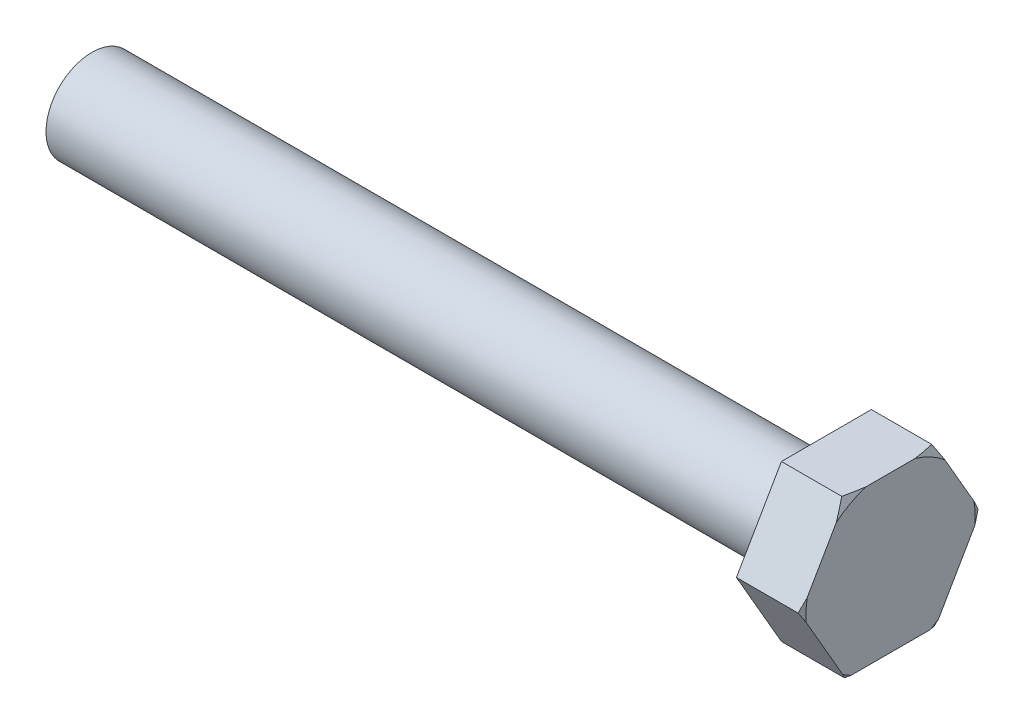
SolidWorks part; units mm, degrees
ref_plane "Front Plane" through (0, 0, 0) normal (0, 0, 1) x (1, 0, 0)
ref_plane "Top Plane" through (0, 0, 0) normal (0, 1, 0) x (1, 0, 0)
ref_plane "Right Plane" through (0, 0, 0) normal (1, 0, 0) x (0, 0, -1)
sketch "Sketch1" plane through (0, 0, 0) normal (1, 0, 0) x (0, 0, -1)
  line L0 (19.6299, 0.6774) -> (9.815, 17.6774)
  line L1 (9.815, 17.6774) -> (-9.815, 17.6774)
  line L2 (-9.815, 17.6774) -> (-19.6299, 0.6774)
  line L3 (-19.6299, 0.6774) -> (-9.815, -16.3226)
  line L4 (-9.815, -16.3226) -> (9.815, -16.3226)
  line L5 (9.815, -16.3226) -> (19.6299, 0.6774)
  circle A0 centre (0, 0.6774) radius 17 construction
  dimension "D1" = 34
extrude "Boss-Extrude1" add sketch "Sketch1" against normal blind 14
sketch "Sketch2" plane through (-14, 0, 0) normal (-1, 0, 0) x (0, 0, 1)
  circle A0 centre (0.2371, 0.1796) radius 10
extrude "Boss-Extrude2" add sketch "Sketch2" along normal blind 160
cosmetic thread "Cosmetic Thread2" parameters "D1"=26, "D2"=17.252
dome "Dome1" faces to dome 1 distance 3 reverse direction no elliptical dome no face at (-174, 0.1796, 10.2371) parameters "D1"=3
sketch "Sketch4" plane through (0, 0, 0) normal (0, 1, 0) x (1, 0, 0)
  line L0 (0, 0) -> (11.4415, 0) construction
  line L5 (0, 18.4633) -> (-1.6327, 21.874)
  line L6 (-1.6327, 21.874) -> (3.8811, 21.2686)
  line L7 (3.8811, 21.2686) -> (2.8757, 18.4633)
  line L8 (2.8757, 18.4633) -> (0, 18.4633)
revolve "Cut-Revolve4" cut sketch "Sketch4" angle 360 about L0
